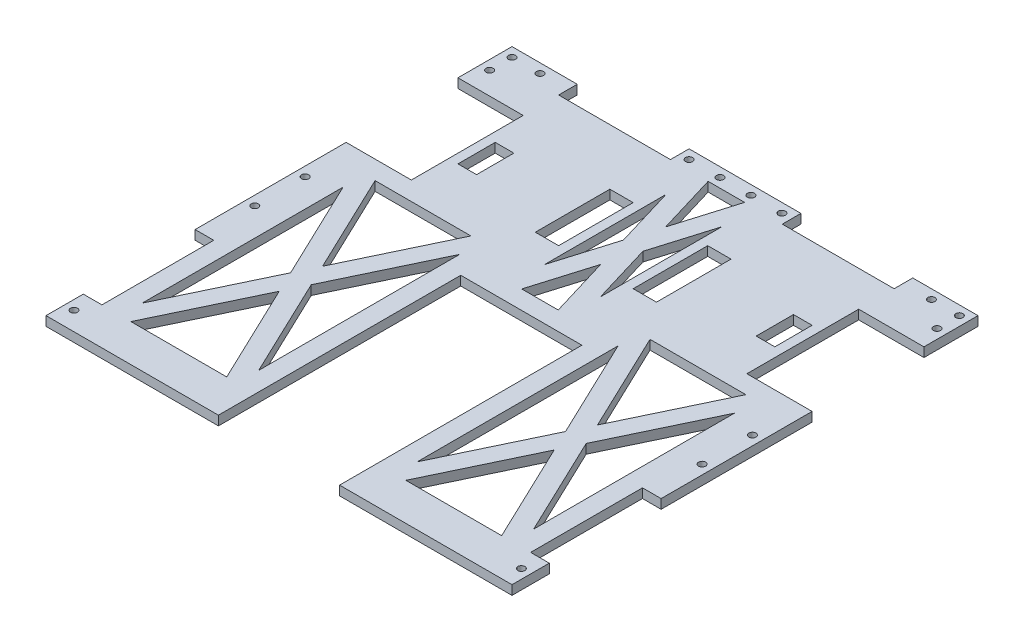
SolidWorks part; units mm, degrees
material "7050-T73510"
ref_plane "Front Plane" through (0, 0, 0) normal (0, 0, 1) x (1, 0, 0)
ref_plane "Top Plane" through (0, 0, 0) normal (0, 1, 0) x (1, 0, 0)
ref_plane "Right Plane" through (0, 0, 0) normal (1, 0, 0) x (0, 0, -1)
sketch "Sketch1" plane through (0, 0, 0) normal (0, 1, 0) x (1, 0, 0)
  line L0 (0, -55) -> (0, 55) construction
  line L1 (-158.75, -76.2) -> (158.75, -76.2)
  line L2 (-158.75, -76.2) -> (-158.75, 76.2)
  line L3 (-158.75, 76.2) -> (158.75, 76.2)
  line L4 (158.75, -76.2) -> (158.75, 76.2)
  line L5 (-158.75, -76.2) -> (158.75, 76.2) construction
  line L6 (-158.75, 76.2) -> (158.75, -76.2) construction
  line L7 (-158.75, -76.2) -> (-25.4, -76.2)
  line L8 (-158.75, -76.2) -> (-158.75, -241.3)
  line L9 (-158.75, -241.3) -> (-25.4, -241.3)
  line L10 (-25.4, -76.2) -> (-25.4, -241.3)
  line L11 (25.4, -76.2) -> (25.4, -241.3)
  line L12 (158.75, -241.3) -> (25.4, -241.3)
  line L13 (158.75, -76.2) -> (158.75, -241.3)
  line L14 (158.75, -76.2) -> (25.4, -76.2)
  line L15 (-41.275, -76.2) -> (-41.275, -241.3)
  line L16 (41.275, -76.2) -> (41.275, -241.3)
  point P0 (0, 0)
  dimension "D1" = 317.5
  dimension "D2" = 152.4
  dimension "D3" = 317.5
  dimension "D4" = 50.8
  dimension "D5" = 15.875
extrude "Boss-Extrude1" add sketch "Sketch1" along normal blind 6.35 contours L15 L1 L8 L9 | L14 L16 L12 L13 | L1 L7 L14 L4 L3 L2 region at (0, 0, 0) region at (-100.0125, 0, 158.75) region at (100.0125, 0, 158.75)
sketch "Sketch2" plane through (0, 6.35, 0) normal (0, 1, 0) x (1, 0, 0)
  line L0 (158.75, -241.3) -> (158.75, 76.2) construction
  line L1 (158.75, 39.37) -> (114.3, 39.37)
  line L2 (158.75, 39.37) -> (158.75, -36.83)
  line L3 (158.75, -36.83) -> (114.3, -36.83)
  line L4 (114.3, 39.37) -> (114.3, -36.83)
  line L5 (-158.75, 76.2) -> (158.75, 76.2) construction
  line L6 (158.75, -139.7) -> (146.05, -139.7)
  line L7 (158.75, -139.7) -> (158.75, -215.9)
  line L8 (158.75, -215.9) -> (146.05, -215.9)
  line L9 (146.05, -139.7) -> (146.05, -215.9)
  line L10 (0, -3.4925) -> (0, 3.4925) construction
  line L11 (-158.75, -215.9) -> (-146.05, -215.9)
  line L12 (-146.05, -139.7) -> (-146.05, -215.9)
  line L13 (-158.75, -139.7) -> (-146.05, -139.7)
  line L14 (-158.75, -139.7) -> (-158.75, -215.9)
  line L15 (-158.75, -36.83) -> (-114.3, -36.83)
  line L16 (-114.3, 39.37) -> (-114.3, -36.83)
  line L17 (-158.75, 39.37) -> (-114.3, 39.37)
  line L18 (-158.75, 39.37) -> (-158.75, -36.83)
  line L19 (-114.3, 63.5) -> (-38.1, 63.5)
  line L20 (114.3, 76.2) -> (38.1, 76.2)
  line L21 (114.3, 76.2) -> (114.3, 63.5)
  line L22 (114.3, 63.5) -> (38.1, 63.5)
  line L23 (38.1, 76.2) -> (38.1, 63.5)
  line L24 (-38.1, 76.2) -> (-38.1, 63.5)
  line L25 (-114.3, 76.2) -> (-38.1, 76.2)
  line L26 (-114.3, 76.2) -> (-114.3, 63.5)
  dimension "D1" = 44.45
  dimension "D2" = 12.7
  dimension "D3" = 76.2
  dimension "D4" = 76.2
  dimension "D5" = 36.83
  dimension "D6" = 215.9
  dimension "D7" = 76.2
  dimension "D8" = 12.7
  dimension "D9" = 76.2
extrude "Cut-Extrude1" cut sketch "Sketch2" against normal through all
sketch "Sketch4" plane through (0, 6.35, 0) normal (0, 1, 0) x (1, 0, 0)
  line L0 (41.275, -76.2) -> (41.275, -241.3) construction
  line L1 (53.975, -215.9) -> (133.35, -215.9)
  line L2 (53.975, -215.9) -> (53.975, -49.53)
  line L3 (53.975, -49.53) -> (133.35, -49.53)
  line L4 (133.35, -215.9) -> (133.35, -49.53)
  line L5 (146.05, -139.7) -> (146.05, -215.9) construction
  line L6 (158.75, -241.3) -> (41.275, -241.3) construction
  line L7 (53.975, -215.9) -> (133.35, -49.53) construction
  line L8 (53.975, -49.53) -> (133.35, -215.9) construction
  line L9 (133.35, -201.1532) -> (61.0107, -49.53)
  line L10 (126.3143, -215.9) -> (53.975, -64.2768)
  line L11 (53.975, -201.1532) -> (126.3143, -49.53)
  line L12 (61.0107, -215.9) -> (133.35, -64.2768)
  line L13 (114.3, -36.83) -> (158.75, -36.83) construction
  line L14 (0, -3.4925) -> (0, 3.4925) construction
  line L15 (-53.975, -201.1532) -> (-126.3143, -49.53)
  line L16 (-126.3143, -215.9) -> (-53.975, -64.2768)
  line L17 (-133.35, -201.1532) -> (-61.0107, -49.53)
  line L18 (-61.0107, -215.9) -> (-133.35, -64.2768)
  line L19 (-53.975, -49.53) -> (-133.35, -49.53)
  line L20 (-133.35, -215.9) -> (-133.35, -49.53)
  line L21 (-53.975, -215.9) -> (-133.35, -215.9)
  line L22 (-53.975, -215.9) -> (-53.975, -49.53)
  point P18 (116.9135, -166.7022)
  dimension "D1" = 12.7
  dimension "D2" = 12.7
  dimension "D3" = 25.4
  dimension "D4" = 12.7
  dimension "D5" = 12.7
extrude "Cut-Extrude3" cut sketch "Sketch4" against normal through all contours L12 L9 L4 | L12 L1 L10 | L2 L11 L10 | L9 L11 L3 | L21 L18 L16 | L20 L17 L18 | L17 L19 L15 | L15 L22 L16 region at (93.6625, 6.35, 193.0873) region at (64.8589, 6.35, 132.715) region at (122.4661, 6.35, 132.715) region at (93.6625, 6.35, 72.3427) region at (-64.8589, 6.35, 132.715) region at (-93.6625, 6.35, 72.3427) region at (-93.6625, 6.35, 193.0873) region at (-122.4661, 6.35, 132.715)
sketch "Sketch3" plane through (0, 6.35, 0) normal (0, 1, 0) x (1, 0, 0)
  line L0 (-41.275, -76.2) -> (41.275, -76.2) construction
  line L1 (-41.275, -25.4) -> (-25.4, -25.4)
  line L2 (-41.275, -25.4) -> (-41.275, 25.4)
  line L3 (-41.275, 25.4) -> (-25.4, 25.4)
  line L4 (-25.4, -25.4) -> (-25.4, 25.4)
  line L5 (0, -3.4925) -> (0, 3.4925) construction
  line L6 (41.275, 25.4) -> (25.4, 25.4)
  line L7 (25.4, -25.4) -> (25.4, 25.4)
  line L8 (41.275, -25.4) -> (25.4, -25.4)
  line L9 (41.275, -25.4) -> (41.275, 25.4)
  line L10 (114.3, 39.37) -> (114.3, -36.83) construction
  line L11 (95.25, 13.97) -> (107.95, 13.97)
  line L12 (95.25, 13.97) -> (95.25, -11.43)
  line L13 (95.25, -11.43) -> (107.95, -11.43)
  line L14 (107.95, 13.97) -> (107.95, -11.43)
  line L15 (38.1, 63.5) -> (114.3, 63.5) construction
  line L16 (-95.25, -11.43) -> (-107.95, -11.43)
  line L17 (-107.95, 13.97) -> (-107.95, -11.43)
  line L18 (-95.25, 13.97) -> (-107.95, 13.97)
  line L19 (-95.25, 13.97) -> (-95.25, -11.43)
  dimension "D1" = 50.8
  dimension "D2" = 15.875
  dimension "D3" = 50.8
  dimension "D4" = 50.8
  dimension "D5" = 25.4
  dimension "D6" = 12.7
  dimension "D7" = 6.35
  dimension "D8" = 49.53
extrude "Cut-Extrude2" cut sketch "Sketch3" against normal through all
sketch "Sketch6" plane through (0, 6.35, 0) normal (0, 1, 0) x (1, 0, 0)
  line L0 (-25.4, -25.4) -> (-25.4, 25.4) construction
  line L1 (-19.05, 63.5) -> (19.05, 63.5)
  line L2 (-19.05, 63.5) -> (-19.05, -63.5)
  line L3 (-19.05, -63.5) -> (19.05, -63.5)
  line L4 (19.05, 63.5) -> (19.05, -63.5)
  line L5 (25.4, 25.4) -> (25.4, -25.4) construction
  line L6 (-38.1, 76.2) -> (38.1, 76.2) construction
  line L7 (-41.275, -76.2) -> (41.275, -76.2) construction
  line L8 (-19.05, -63.5) -> (19.05, 63.5) construction
  line L9 (19.05, -63.5) -> (-19.05, 63.5) construction
  line L10 (12.4204, -63.5) -> (-19.05, 41.4014)
  line L11 (-12.4204, 63.5) -> (19.05, -41.4014)
  line L12 (-19.05, -41.4014) -> (12.4204, 63.5)
  line L13 (19.05, 41.4014) -> (-12.4204, -63.5)
  dimension "D1" = 6.35
  dimension "D2" = 6.35
  dimension "D3" = 12.7
  dimension "D4" = 12.7
  dimension "D5" = 12.7
  dimension "D6" = 12.7
extrude "Cut-Extrude5" cut sketch "Sketch6" against normal through all contours L10 L13 L3 | L4 L13 L11 | L2 L12 L10 | L11 L12 L1 region at (0, 6.35, -49.6995) region at (-14.9099, 6.35, 0) region at (14.9099, 6.35, 0) region at (0, 6.35, 49.6995)
sketch "Sketch7" plane through (0, 6.35, 0) normal (0, 1, 0) x (1, 0, 0)
  line L0 (158.75, -139.7) -> (146.05, -139.7) construction
  line L1 (158.75, -139.7) -> (158.75, -36.83) construction
  line L2 (0, -3.4925) -> (0, 3.4925) construction
  line L3 (158.75, -241.3) -> (41.275, -241.3) construction
  line L4 (-38.1, 76.2) -> (-38.1, 63.5) construction
  line L5 (114.3, 76.2) -> (158.75, 76.2) construction
  line L6 (-38.1, 76.2) -> (38.1, 76.2) construction
  circle A0 centre (152.4, -105.41) radius 2.413
  circle A1 centre (152.4, -71.12) radius 2.413
  circle A8 centre (152.4, -228.6) radius 2.413
  circle A9 centre (152.4, 69.85) radius 2.413
  circle A10 centre (133.35, 69.85) radius 2.413
  circle A12 centre (152.4, 54.61) radius 2.413
  circle A19 centre (-152.4, -228.6) radius 2.413
  circle A20 centre (-31.75, 69.85) radius 2.413
  circle A21 centre (-10.668, 69.85) radius 2.413
  circle A22 centre (10.414, 69.85) radius 2.413
  circle A23 centre (31.496, 69.85) radius 2.413
  circle A24 centre (-152.4, 54.61) radius 2.413
  circle A25 centre (-133.35, 69.85) radius 2.413
  circle A26 centre (-152.4, 69.85) radius 2.413
  circle A27 centre (-152.4, -71.12) radius 2.413
  circle A28 centre (-152.4, -105.41) radius 2.413
  dimension "D1" = 4.826
  dimension "D3" = 6.35
  dimension "D5" = 12.7
  dimension "D6" = 6.35
  dimension "D9" = 4.826
  dimension "D2" = 34.29
  dimension "D8" = 2
  dimension "D10" = 6.35
  dimension "D11" = 6.35
  dimension "D4" = 2
  dimension "D7" = 2
  dimension "D12" = 4
extrude "Cut-Extrude6" cut sketch "Sketch7" against normal through all
sketch "Sketch5" plane through (0, 6.35, 0) normal (0, 1, 0) x (1, 0, 0)
  line L0 (0, -3.4925) -> (0, 3.4925) construction
  line L2 (-38.1, 76.2) -> (38.1, 76.2) construction
  line L3 (41.275, -25.4) -> (41.275, 25.4) construction
  line L4 (114.3, 63.5) -> (38.1, 63.5) construction
  circle A0 centre (12.7, 63.5) radius 6.35
  circle A1 centre (12.7, 50.8) radius 6.35
  circle A2 centre (12.7, 38.1) radius 6.35
  circle A3 centre (12.7, 25.4) radius 6.35
  circle A4 centre (12.7, 12.7) radius 6.35
  circle A11 centre (0, 50.8) radius 6.35
  circle A12 centre (0, 38.1) radius 6.35
  circle A13 centre (0, 25.4) radius 6.35
  circle A14 centre (0, 12.7) radius 6.35
  circle A21 centre (-12.7, 50.8) radius 6.35
  circle A22 centre (-12.7, 38.1) radius 6.35
  circle A23 centre (-12.7, 25.4) radius 6.35
  circle A24 centre (-12.7, 12.7) radius 6.35
  circle A31 centre (0, 63.5) radius 6.35
  circle A32 centre (-12.7, 63.5) radius 6.35
  circle A33 centre (53.975, 50.8) radius 3.175
  circle A34 centre (66.675, 50.8) radius 3.175
  circle A35 centre (79.375, 50.8) radius 3.175
  circle A36 centre (66.675, 38.1) radius 3.175
  circle A37 centre (79.375, 38.1) radius 3.175
  circle A38 centre (66.675, 25.4) radius 3.175
  circle A39 centre (79.375, 25.4) radius 3.175
  circle A40 centre (66.675, 12.7) radius 3.175
  circle A41 centre (79.375, 12.7) radius 3.175
  circle A42 centre (66.675, 0) radius 3.175
  circle A43 centre (79.375, 0) radius 3.175
  circle A44 centre (66.675, -12.7) radius 3.175
  circle A45 centre (79.375, -12.7) radius 3.175
  circle A46 centre (66.675, -25.4) radius 3.175
  circle A47 centre (79.375, -25.4) radius 3.175
  circle A48 centre (66.675, -38.1) radius 3.175
  circle A49 centre (79.375, -38.1) radius 3.175
  circle A50 centre (53.975, 38.1) radius 3.175
  circle A51 centre (53.975, 25.4) radius 3.175
  circle A52 centre (53.975, 12.7) radius 3.175
  circle A53 centre (53.975, 0) radius 3.175
  circle A54 centre (53.975, -12.7) radius 3.175
  circle A55 centre (53.975, -25.4) radius 3.175
  circle A56 centre (53.975, -38.1) radius 3.175
  circle A57 centre (-53.975, -38.1) radius 3.175
  circle A58 centre (-53.975, -25.4) radius 3.175
  circle A59 centre (-53.975, -12.7) radius 3.175
  circle A60 centre (-53.975, 0) radius 3.175
  circle A61 centre (-53.975, 12.7) radius 3.175
  circle A62 centre (-53.975, 25.4) radius 3.175
  circle A63 centre (-53.975, 38.1) radius 3.175
  circle A64 centre (-79.375, -38.1) radius 3.175
  circle A65 centre (-66.675, -38.1) radius 3.175
  circle A66 centre (-79.375, -25.4) radius 3.175
  circle A67 centre (-66.675, -25.4) radius 3.175
  circle A68 centre (-79.375, -12.7) radius 3.175
  circle A69 centre (-66.675, -12.7) radius 3.175
  circle A70 centre (-79.375, 0) radius 3.175
  circle A71 centre (-66.675, 0) radius 3.175
  circle A72 centre (-79.375, 12.7) radius 3.175
  circle A73 centre (-66.675, 12.7) radius 3.175
  circle A74 centre (-79.375, 25.4) radius 3.175
  circle A75 centre (-66.675, 25.4) radius 3.175
  circle A76 centre (-79.375, 38.1) radius 3.175
  circle A77 centre (-66.675, 38.1) radius 3.175
  circle A78 centre (-79.375, 50.8) radius 3.175
  circle A79 centre (-66.675, 50.8) radius 3.175
  circle A80 centre (-53.975, 50.8) radius 3.175
  dimension "D1" = 12.7
  dimension "D6" = 6.35
  dimension "D2" = 12.7
  dimension "D3" = 12.7
  dimension "D7" = 12.7
  dimension "D8" = 12.7
  dimension "D4" = 5
  dimension "D5" = 3
  dimension "D9" = 3
  dimension "D10" = 8
